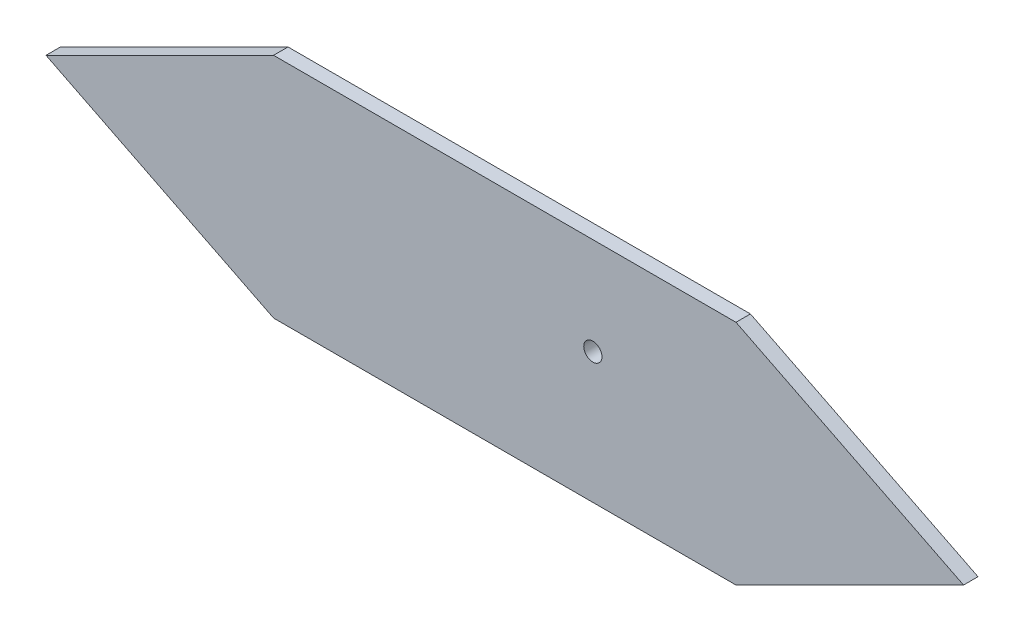
SolidWorks part; units mm, degrees
material "AISI 316 Annealed Stainless Steel Bar (SS)"
ref_plane "Front Plane" through (0, 0, 0) normal (0, 0, 1) x (1, 0, 0)
ref_plane "Top Plane" through (0, 0, 0) normal (0, 1, 0) x (1, 0, 0)
ref_plane "Right Plane" through (0, 0, 0) normal (1, 0, 0) x (0, 0, -1)
sketch "Sketch1" plane through (0, 0, 0) normal (0, 0, 1) x (1, 0, 0)
  line L0 (0, 50) -> (-100, 50) construction
  line L1 (0, 0) -> (203.2, 0)
  line L2 (0, 0) -> (0, 100)
  line L3 (0, 100) -> (203.2, 100)
  line L4 (203.2, 0) -> (203.2, 100)
  line L5 (101.6, 0) -> (101.6, 100) construction
  line L6 (0, 100) -> (-100, 50)
  line L7 (-100, 50) -> (0, 0)
  line L8 (303.2, 50) -> (203.2, 0)
  line L9 (203.2, 100) -> (303.2, 50)
  dimension "D3" = 100
  dimension "D1" = 203.2
  dimension "D2" = 100
extrude "Boss-Extrude1" add sketch "Sketch1" along normal blind 6.35 contours L2 | L4 | L1 L4 L3 L2 region at (101.6, 50, 0) region at (-33.3333, 50, 0) region at (236.5333, 50, 0)
sketch "Sketch2" plane through (0, 0, 0) normal (0, 0, -1) x (-1, 0, 0)
  line L0 (0, 0) -> (-203.2, 0) construction
  line L5 (-203.2, 6.7) -> (-177.8, 6.7)
  line L6 (-203.2, 6.7) -> (-203.2, 12.7)
  line L7 (-203.2, 12.7) -> (-177.8, 12.7)
  line L8 (-177.8, 6.7) -> (-177.8, 12.7)
  line L9 (6, 25.05) -> (6, 6.7)
  line L10 (-101.6, 0) -> (-101.6, 100) construction
  line L11 (0, 100) -> (-203.2, 100) construction
  line L20 (0, 6.7) -> (6, 6.7)
  line L21 (-203.2, 19.05) -> (-177.8, 19.05)
  line L22 (-203.2, 19.05) -> (-203.2, 25.05)
  line L23 (-203.2, 25.05) -> (-177.8, 25.05)
  line L24 (-177.8, 19.05) -> (-177.8, 25.05)
  line L25 (-203.2, 19.05) -> (-203.2, 12.7)
  line L26 (-203.2, 25.05) -> (-209.2, 25.05)
  line L31 (-203.2, 25.05) -> (-203.2, 6.7)
  line L36 (-203.2, 6.7) -> (-209.2, 6.7)
  line L37 (-209.2, 25.05) -> (-209.2, 6.7)
  line L38 (0, 25.05) -> (0, 6.7)
  line L39 (0, 25.05) -> (6, 25.05)
  line L40 (0, 19.05) -> (0, 12.7)
  line L41 (-25.4, 19.05) -> (-25.4, 25.05)
  line L50 (0, 25.05) -> (-25.4, 25.05)
  line L51 (0, 19.05) -> (0, 25.05)
  line L52 (0, 19.05) -> (-25.4, 19.05)
  line L53 (-25.4, 6.7) -> (-25.4, 12.7)
  line L54 (0, 12.7) -> (-25.4, 12.7)
  line L55 (0, 6.7) -> (0, 12.7)
  line L56 (0, 6.7) -> (-25.4, 6.7)
  dimension "D1" = 25.4
  dimension "D2" = 6.35
  dimension "D3" = 12.7
  dimension "D4" = 6
  dimension "D5" = 6
  dimension "D6" = 6
  dimension "D7" = 101.6
extrude "Boss-Extrude3" add sketch "Sketch2" along normal blind 25 contours L21 L24 L23 L22 | L26 L37 L36 L6 L25 L22 | L41 | L39 L38 L20 L9 | L56 L38 L54 L53 | L6 L5 L8 L7 region at (206.2, 15.875, 0) region at (190.5, 22.05, 0) region at (-3, 15.875, 0) region at (12.7, 22.05, 0) region at (12.7, 9.7, 0)
sketch "Sketch3" plane through (0, 0, 0) normal (0, 0, -1) x (-1, 0, 0)
  circle A0 centre (-140.3, 57.4) radius 4
  dimension "D1" = 8
  dimension "D2" = 62.9
  dimension "D3" = 38.35
extrude "Cut-Extrude1" cut sketch "Sketch3" against normal blind 25
